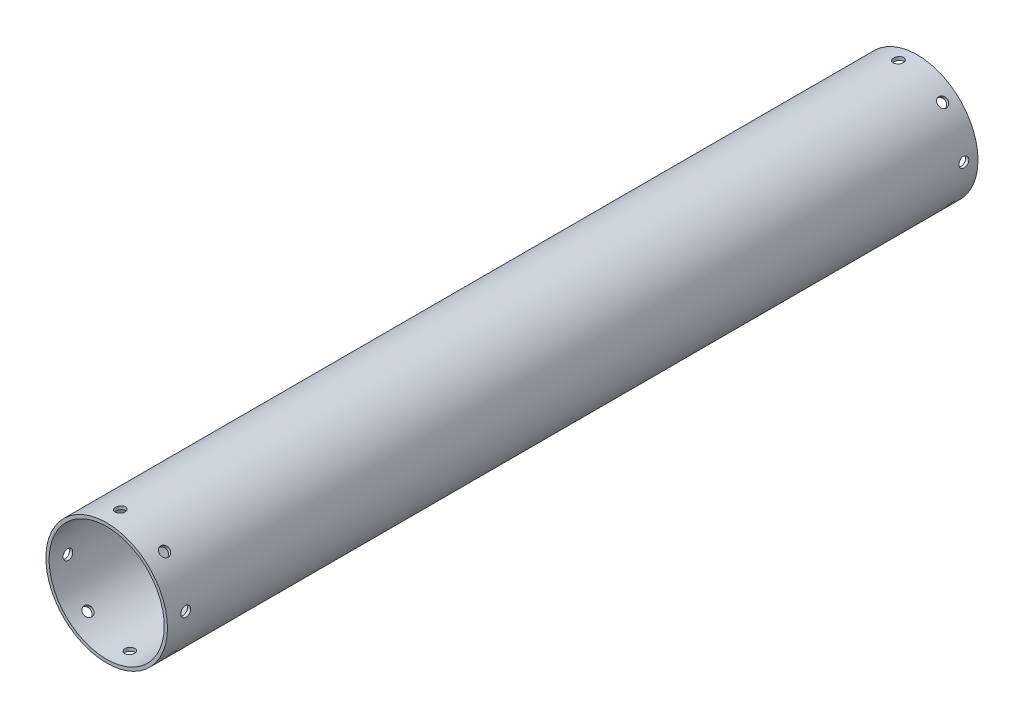
SolidWorks part; units mm, degrees
note: '?' marks a value the reader was unsure of.
ref_plane "Front Plane" through (0, 0, 0) normal (0, 0, 1) x (1, 0, 0)
ref_plane "Top Plane" through (0, 0, 0) normal (0, 1, 0) x (1, 0, 0)
ref_plane "Right Plane" through (0, 0, 0) normal (1, 0, 0) x (0, 0, -1)
sketch "Sketch1" plane through (0, 0, 0) normal (0, 0, 1) x (1, 0, 0)
  circle A0 centre (0, 0) radius 37.5
  circle A1 centre (0, 0) radius 35.5
  dimension "D1" = 75
  dimension "D2" = 71
extrude "Boss-Extrude1" add sketch "Sketch1" along normal blind 500
hole_wizard "1/4 (0.236) Diameter Hole1" positions "3DSketch2" profile "Sketch4" hole size "1/4" standard "ANSI Inch"
sketch3d "3DSketch2"
  point P0 (-3.0322, 37.3772, 488.5629)
  point P6 (11.2197, -65.3586, 0)
  dimension "D1" = 490
sketch "Sketch4" plane through (-3.0322, 37.3772, 488.5629) normal (0, 0, 1) x (-0.9967, -0.0809, 0)
  line L0 (0, 0) -> (0, 6.1)
  line L1 (0, 6.1) -> (2.9972, 4.2991)
  line L2 (2.9972, 4.2991) -> (2.9972, 0)
  line L5 (2.9972, 0) -> (0, 0)
  line L10 (0, 6.1) -> (-2.9972, 4.2991) construction
  line L11 (0, -6.35) -> (0, 107.95) construction
  dimension "Hole Dia." = 5.9944
  dimension "Hole Depth" = 6.1
  dimension "Drill Angle" = 118
pattern_circular "CirPattern1" count 8 over 360 about axis through (0, 0, 500) along (0, 0, -1) of "1/4 (0.236) Diameter Hole1"
ref_plane "Plane1" through (0, 0, 570) normal (0, 0, 1) x (1, 0, 0)
ref_axis "Axis1" through (0, 0, 500) along (0, 0, -1)?
pattern_linear "LPattern1" count 2 spacing 480 along (0, 0, -1) of "CirPattern1", "1/4 (0.236) Diameter Hole1"
